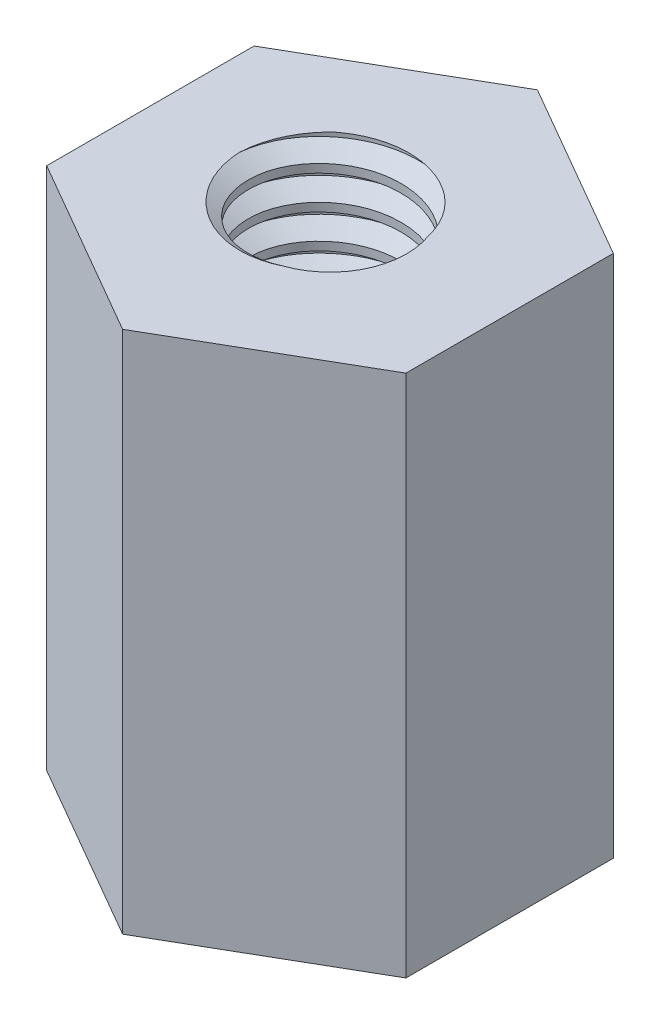
SolidWorks part; units mm, degrees
ref_plane "Front Plane" through (0, 0, 0) normal (0, 0, 1) x (1, 0, 0)
ref_plane "Top Plane" through (0, 0, 0) normal (0, 1, 0) x (1, 0, 0)
ref_plane "Right Plane" through (0, 0, 0) normal (1, 0, 0) x (0, 0, -1)
sketch "Sketch1" plane through (0, 0, 0) normal (0, 1, 0) x (1, 0, 0)
  line L1 (2.4, 1.3856) -> (0, 2.7713)
  line L2 (0, 2.7713) -> (-2.4, 1.3856)
  line L3 (-2.4, 1.3856) -> (-2.4, -1.3856)
  line L4 (-2.4, -1.3856) -> (0, -2.7713)
  line L5 (0, -2.7713) -> (2.4, -1.3856)
  line L6 (2.4, -1.3856) -> (2.4, 1.3856)
  circle A0 centre (0, 0) radius 2.4 construction
  circle A1 centre (0, 0) radius 1.025
  dimension "D1" = 4.8
  dimension "D2" = 2.05
extrude "Boss-Extrude1" add sketch "Sketch1" along normal blind 7
thread "Thread1" pitch 0.45 method cut profile "Thread Profile1" start angle 0, offset 2, length 12, pitch 0.45, diameter 2.05
ref_plane "Plane1" through (-1.025, 9, 0) normal (0, 0, 1) x (-1, 0, 0)
sketch "Thread Profile1" plane through (-1.025, 9, 0) normal (0, 0, 1) x (-1, 0, 0)
  line L0 (0, 0) -> (0, 0.45) construction
  line L1 (0, 0) -> (0.2436, 0.1406)
  line L2 (0.2436, 0.1406) -> (0.2436, 0.1969)
  line L3 (0.2436, 0.1969) -> (0, 0.3375)
  line L4 (0.2436, 0.1687) -> (0, 0.1687) construction
  line L11 (0, 0) -> (0, 0.3375)
  point P2 (0, 0)
  dimension "Pitch" = 0.45
  dimension "Profile_Angle" = 60
  dimension "Profile_Land" = 0.0562
  dimension "Profile_Height" = 0.2436
